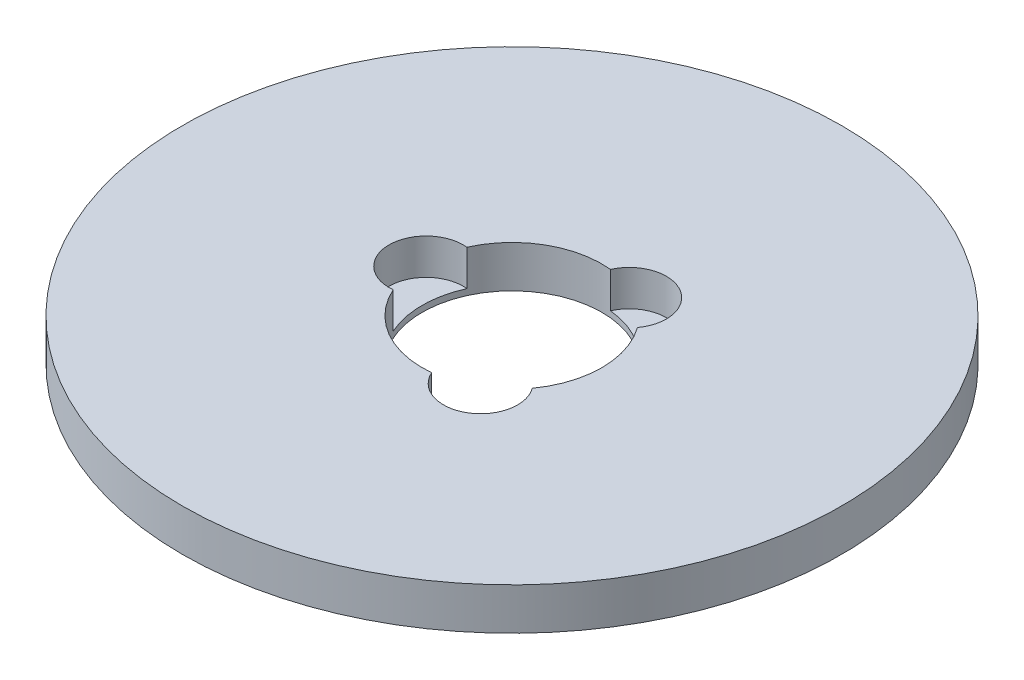
SolidWorks part; units mm, degrees
ref_plane "Front Plane" through (0, 0, 0) normal (0, 0, 1) x (1, 0, 0)
ref_plane "Top Plane" through (0, 0, 0) normal (0, 1, 0) x (1, 0, 0)
ref_plane "Right Plane" through (0, 0, 0) normal (1, 0, 0) x (0, 0, -1)
sketch "Sketch1" plane through (0, 0, 0) normal (0, 1, 0) x (1, 0, 0)
  circle A0 centre (0, 0) radius 55
  dimension "FLANGE_OD" = 110
extrude "Boss-Extrude1" add sketch "Sketch1" along normal blind 7
sketch "Sketch2" plane through (0, 0, 0) normal (0, 1, 0) x (1, 0, 0)
  circle A0 centre (0, 0) radius 15
  dimension "BORE_D" = 30
extrude "Cut-Extrude1" cut sketch "Sketch2" along normal through all
sketch "Sketch3" plane through (0, 7, 0) normal (0, 1, 0) x (1, 0, 0)
  circle A0 centre (0, 0) radius 14.3318 construction
  circle A1 centre (-14.3318, 0) radius 6.1832
  dimension "BOLT_D" = 12.3665
  dimension "BOLT_PCD" = 28.6635
extrude "Cut-Extrude2" cut sketch "Sketch3" against normal blind 5.9836
pattern_circular "CirPattern1" count 3 over 360 about axis through (0, 0, 0) along (0, 1, 0) of "Cut-Extrude2"
